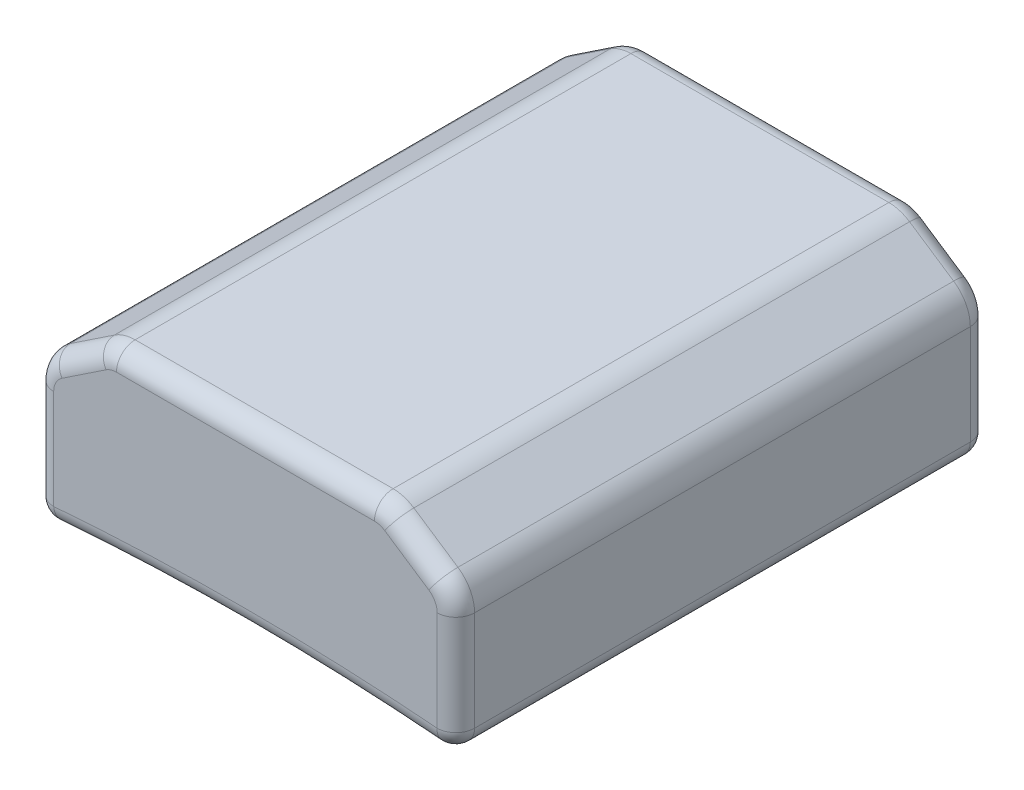
SolidWorks part; units mm, degrees
ref_plane "Alzado" through (0, 0, 0) normal (0, 0, 1) x (1, 0, 0)
ref_plane "Planta" through (0, 0, 0) normal (0, 1, 0) x (1, 0, 0)
ref_plane "Vista lateral" through (0, 0, 0) normal (1, 0, 0) x (0, 0, -1)
sketch "Croquis1" plane through (0, 0, 0) normal (0, 0, 1) x (1, 0, 0)
  line L0 (0, 0.0318) -> (0, 15)
  line L1 (45, 0) -> (45, 15)
  line L2 (0, 15) -> (7.5007, 20)
  line L3 (37.5007, 20) -> (45, 15)
  line L4 (22.5007, 20) -> (7.5007, 20)
  line L5 (22.5007, 20) -> (37.5007, 20)
  arc A0 (0, 0.0318) -> (45, 0) centre (22.3206, -253.724) cw
extrude "Saliente-Extruir1" add sketch "Croquis1" along normal blind 57
sketch "Croquis3" plane through (0, 0, 0) normal (0, 0, 1) x (1, 0, 0)
  line L4 (4.8597, 15.8359) -> (2, 13.9296)
  line L8 (2, 7.5159) -> (2, 13.9296)
  line L10 (22.5007, 18.0122) -> (8.1246, 18.0122)
  line L11 (2, 7.5159) -> (2, 3.0115)
  line L12 (22.5007, 3.0115) -> (2, 3.0115)
  line L13 (22.5007, 3.0115) -> (43, 3.0115)
  line L14 (43, 3.0115) -> (43, 7.5)
  line L15 (4.8597, 15.8359) -> (8.1246, 18.0122)
  line L16 (36.8767, 18.0122) -> (22.5007, 18.0122)
  line L17 (40.1409, 15.8359) -> (36.8767, 18.0122)
  line L18 (40.1409, 15.8359) -> (43, 13.9297)
  line L19 (43, 7.5) -> (43, 13.9297)
  point P8 (0, 0)
extrude "Cortar-Extruir1" cut sketch "Croquis3" along normal blind 55
fillet "Redondeo11" radius 4 4 edges at (0, 15, 28.5) (7.5007, 20, 28.5) (45, 15, 28.5) (37.5007, 20, 28.5)
fillet "Redondeo13" radius 2 2 edges at (45, 0, 28.5) (0, 0.0318, 28.5)
fillet "Redondeo14" radius 2 23 edges at (37.4487, 19.8283, 57) (44.5267, 14.7467, 57) (44.3561, 0.7073, 57) (0.6429, 0.737, 57) (0.4733, 14.7467, 57) (7.5527, 19.8284, 57) (37.4487, 19.8283, 0) (44.5267, 14.7467, 0) (44.3561, 0.7073, 0) (0.6429, 0.737, 0) (0.4733, 14.7467, 0) (4.1372, 17.7579, 0) (7.5527, 19.8284, 0) (4.1372, 17.7579, 57) (0, 7.5326, 57) (22.4992, 1.0115, 57) (45, 7.5184, 57) (40.8637, 17.7578, 57) (22.5006, 20, 57) (0, 7.5326, 0) (22.4992, 1.0115, 0) (45, 7.5184, 0) (40.8637, 17.7578, 0)
